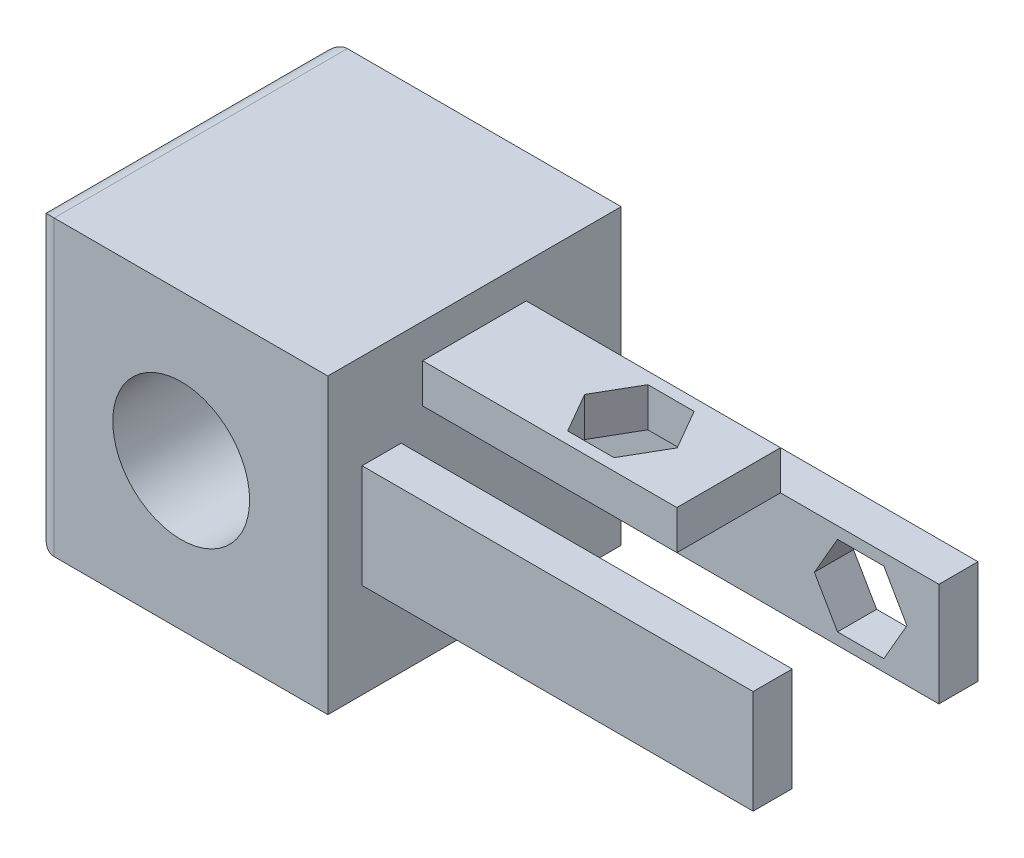
SolidWorks part; units mm, degrees
ref_plane "Plano frontal" through (0, 0, 0) normal (0, 0, 1) x (1, 0, 0)
ref_plane "Plano superior" through (0, 0, 0) normal (0, 1, 0) x (1, 0, 0)
ref_plane "Plano direito" through (0, 0, 0) normal (1, 0, 0) x (0, 0, -1)
sketch "Esboço1" plane through (0, 0, 0) normal (0, 0, 1) x (1, 0, 0)
  line L1 (-7.5, 7.5) -> (7.5, 7.5)
  line L2 (-7.5, 7.5) -> (-7.5, -7.5)
  line L3 (-7.5, -7.5) -> (7.5, -7.5)
  line L4 (7.5, 7.5) -> (7.5, -7.5)
  line L5 (-7.5, 7.5) -> (7.5, -7.5) construction
  line L6 (-7.5, -7.5) -> (7.5, 7.5) construction
  circle A0 centre (0, 0) radius 1.75
  circle A1 centre (0, 0) radius 3.5
  point P0 (0, 0)
  dimension "D1" = 3.5
  dimension "D3" = 7
  dimension "D2" = 15
extrude "Ressalto-extrusão1" add sketch "Esboço1" along normal mid plane 15 contours L4 L1 L2 L3 A1 region at (0, 7.2879, 0)
sketch "Esboço2" plane through (7.5, 0, 0) normal (1, 0, 0) x (0, 0, -1)
  line L0 (-7.5, 7.5) -> (7.5, -7.5) construction
  circle A0 centre (0, 0) radius 3.5
  circle A1 centre (0, 0) radius 1.6
  dimension "D1" = 3.2
  dimension "D2" = 7
extrude "Corte-extrusão1" [suppressed] cut sketch "Esboço2" against normal through all contours A0
sketch "Esboço4" plane through (0, 7.5, 0) normal (0, 1, 0) x (1, 0, 0)
  circle A0 centre (0, 0) radius 3.5
  circle A1 centre (0, 0) radius 1.6
  dimension "D1" = 7
  dimension "D2" = 3.2
extrude "Corte-extrusão2" [suppressed] cut sketch "Esboço4" against normal through all both and the other way through all contours A0
extrude "Ressalto-extrusão2" add sketch "Esboço1<3>" along normal blind 3 from surface contours A1 A0 region at (-3.401, 0, 0) starting at face at (3.5, 0, -7.5)
sketch "Esboço1<3>" plane through (0, 0, 0) normal (0, 0, 1) x (1, 0, 0) same geometry as "Esboço1"
extrude "Ressalto-extrusão3" add sketch "Esboço2<3>" against normal blind 3
sketch "Esboço2<3>" plane through (7.5, 0, 0) normal (1, 0, 0) x (0, 0, -1) same geometry as "Esboço2"
extrude "Ressalto-extrusão4" add sketch "Esboço4<3>" against normal blind 3
sketch "Esboço4<3>" plane through (0, 7.5, 0) normal (0, 1, 0) x (1, 0, 0) same geometry as "Esboço4"
sketch "Esboço6" plane through (7.5, 0, 0) normal (1, 0, 0) x (0, 0, -1)
  line L0 (0, 4.1562) -> (0, 0) construction
  line L1 (0, 0) -> (3.2125, 0) construction
  line L3 (-2.65, 3.75) -> (2.65, 3.75)
  line L4 (-2.65, 3.75) -> (-2.65, 5.75)
  line L5 (-2.65, 5.75) -> (2.65, 5.75)
  line L6 (2.65, 3.75) -> (2.65, 5.75)
  line L7 (-2.65, 3.75) -> (2.65, 5.75) construction
  line L8 (-2.65, 5.75) -> (2.65, 3.75) construction
  line L9 (3.75, 2.65) -> (3.75, -2.65)
  line L10 (3.75, 2.65) -> (5.75, 2.65)
  line L11 (5.75, 2.65) -> (5.75, -2.65)
  line L12 (3.75, -2.65) -> (5.75, -2.65)
  line L13 (3.75, 2.65) -> (5.75, -2.65) construction
  line L14 (5.75, 2.65) -> (3.75, -2.65) construction
  line L15 (2.65, -3.75) -> (-2.65, -3.75)
  line L16 (2.65, -3.75) -> (2.65, -5.75)
  line L17 (2.65, -5.75) -> (-2.65, -5.75)
  line L18 (-2.65, -3.75) -> (-2.65, -5.75)
  line L19 (2.65, -3.75) -> (-2.65, -5.75) construction
  line L20 (2.65, -5.75) -> (-2.65, -3.75) construction
  line L21 (-3.75, -2.65) -> (-3.75, 2.65)
  line L22 (-3.75, -2.65) -> (-5.75, -2.65)
  line L23 (-5.75, -2.65) -> (-5.75, 2.65)
  line L24 (-3.75, 2.65) -> (-5.75, 2.65)
  line L25 (-3.75, -2.65) -> (-5.75, 2.65) construction
  line L26 (-5.75, -2.65) -> (-3.75, 2.65) construction
  point P3 (0, 4.75)
  point P11 (4.75, 0)
  point P18 (0, -4.75)
  point P23 (-4.75, 0)
  point P28 (0, 0)
  dimension "D1" = 2
  dimension "D2" = 5.3
  dimension "D4" = 11.5
  dimension "D3" = 4
extrude "Ressalto-extrusão5" add sketch "Esboço6" along normal blind 20
sketch "Esboço7" plane through (0, -7.5, 0) normal (0, -1, 0) x (1, 0, 0)
  line L0 (20.5, 2.65) -> (20.5, -2.65)
  line L1 (27.5, 2.65) -> (7.5, 2.65) construction
  line L2 (17.8671, 0) -> (16.6836, 2.05)
  line L3 (16.6836, 2.05) -> (14.3164, 2.05)
  line L4 (14.3164, 2.05) -> (13.1329, 0)
  line L5 (13.1329, 0) -> (14.3164, -2.05)
  line L6 (14.3164, -2.05) -> (16.6836, -2.05)
  line L7 (16.6836, -2.05) -> (17.8671, 0)
  line L8 (27.5, 2.65) -> (27.5, -2.65) construction
  line L9 (27.5, -2.65) -> (7.5, -2.65) construction
  line L10 (20.5, -2.65) -> (27.5, -2.65)
  line L11 (27.5, -2.65) -> (27.5, 2.65)
  line L12 (27.5, 2.65) -> (20.5, 2.65)
  circle A1 centre (15.5, 0) radius 2.05 construction
  dimension "D2" = 12
  dimension "D1" = 4.1
  dimension "D3" = 7
extrude "Corte-extrusão3" cut sketch "Esboço7" against normal through all both and the other way through all
sketch "Esboço8" plane through (0, 0, -5.75) normal (0, 0, -1) x (-1, 0, 0)
  line L0 (-14.3164, -5.75) -> (-16.6836, -5.75) construction
  line L1 (-25.8671, 0) -> (-24.6836, -2.05)
  line L2 (-24.6836, -2.05) -> (-22.3164, -2.05)
  line L3 (-22.3164, -2.05) -> (-21.1329, 0)
  line L4 (-21.1329, 0) -> (-22.3164, 2.05)
  line L5 (-22.3164, 2.05) -> (-24.6836, 2.05)
  line L6 (-24.6836, 2.05) -> (-25.8671, 0)
  line L7 (-27.5, -2.65) -> (-27.5, 2.65) construction
  circle A0 centre (-23.5, 0) radius 2.05 construction
  dimension "D1" = 4
extrude "Corte-extrusão4" cut sketch "Esboço8" against normal blind 3
fillet "Filete1" radius 1 4 edges at (-7.5, 0, -7.5) (-7.5, -7.5, 0) (-7.5, 7.5, 0) (-7.5, 0, 7.5)
